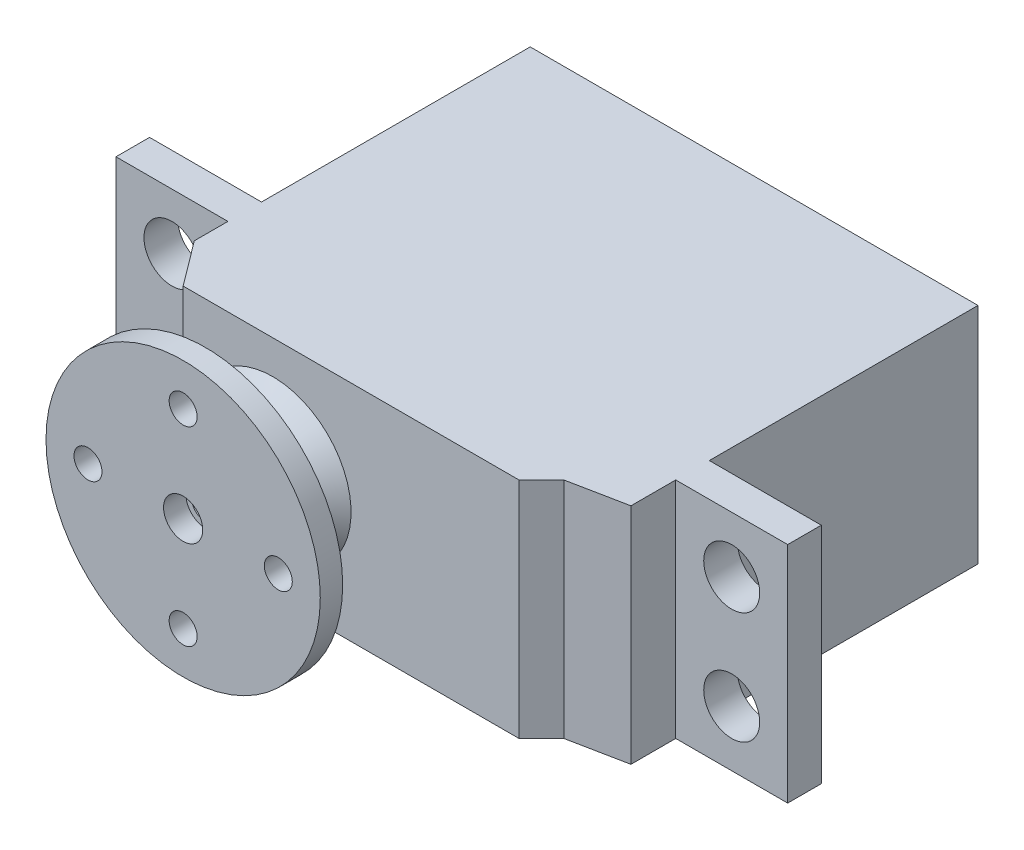
SolidWorks part; units mm, degrees
ref_plane "前视基准面" through (0, 0, 0) normal (0, 0, 1) x (1, 0, 0)
ref_plane "上视基准面" through (0, 0, 0) normal (0, 1, 0) x (1, 0, 0)
ref_plane "右视基准面" through (0, 0, 0) normal (1, 0, 0) x (0, 0, -1)
sketch "草图1" plane through (0, 0, 0) normal (0, 0, 1) x (1, 0, 0)
  line L1 (-20, -10) -> (20, -10)
  line L2 (-20, -10) -> (-20, 10)
  line L3 (-20, 10) -> (20, 10)
  line L4 (20, -10) -> (20, 10)
  line L5 (0, 10) -> (0, -10) construction
  line L6 (-20, 0) -> (20, 0) construction
  point P0 (0, 0)
  dimension "D1" = 40
  dimension "D2" = 20
extrude "凸台-拉伸1" add sketch "草图1" along normal blind 37
sketch "草图2" plane through (0, -10, 0) normal (0, -1, 0) x (1, 0, 0)
  line L0 (20, 34) -> (15, 35)
  line L1 (20, 37) -> (20, 0) construction
  line L2 (15, 35) -> (13, 37)
  line L3 (-20, 37) -> (20, 37) construction
  line L4 (13, 37) -> (20, 37)
  line L5 (20, 37) -> (20, 34)
  dimension "D1" = 3
  dimension "D2" = 2
  dimension "D3" = 2
  dimension "D4" = 5
extrude "切除-拉伸1" cut sketch "草图2" against normal through all
sketch "草图3" plane through (0, -10, 0) normal (0, -1, 0) x (1, 0, 0)
  line L0 (-20, 37) -> (-17, 37)
  line L1 (-20, 37) -> (13, 37) construction
  line L2 (-17, 37) -> (-20, 33)
  line L3 (-20, 37) -> (-20, 0) construction
  line L4 (-20, 33) -> (-20, 37)
  dimension "D1" = 3
  dimension "D2" = 4
extrude "切除-拉伸2" cut sketch "草图3" against normal through all
chamfer "倒角1" distance 3 angle 45 4 edges at (20, 0, 0) (0, 10, 0) (-20, 0, 0) (0, -10, 0)
sketch "草图4" plane through (0, 0, 37) normal (0, 0, 1) x (1, 0, 0)
  line L0 (-17, 10) -> (-17, -10) construction
  line L1 (13, 0) -> (-22.6233, 0) construction
  line L2 (13, 10) -> (13, -10) construction
  circle A0 centre (-9, 0) radius 7
  dimension "D1" = 14
  dimension "D2" = 8
extrude "凸台-拉伸2" add sketch "草图4" along normal blind 2
chamfer "倒角2" distance 2 angle 45 1 edges at (-2, 0, 39)
sketch "草图5" plane through (0, 0, 39) normal (0, 0, 1) x (1, 0, 0)
  circle A0 centre (-9, 0) radius 3
  dimension "D1" = 6
extrude "凸台-拉伸3" add sketch "草图5" along normal blind 4
ref_plane "基准面1" through (0, 0, 30) normal (0, 0, -1) x (-1, 0, 0)
sketch "草图6" plane through (0, 0, 30) normal (0, 0, -1) x (-1, 0, 0)
  line L0 (20, 10) -> (20, -10)
  line L1 (20, 10) -> (30, 10)
  line L2 (20, -10) -> (30, -10)
  line L3 (30, 10) -> (30, -10)
  line L4 (-20, 10) -> (-20, -10)
  line L5 (-20, 10) -> (-30, 10)
  line L6 (-20, -10) -> (-30, -10)
  line L7 (-30, 10) -> (-30, -10)
  dimension "D1" = 10
  dimension "D2" = 10
extrude "凸台-拉伸4" add sketch "草图6" along normal blind 3
sketch "草图7" plane through (0, 0, 30) normal (0, 0, 1) x (1, 0, 0)
  line L0 (-25, -8.7626) -> (-25, 14.1579) construction
  line L1 (-30, 10) -> (-20, 10) construction
  line L2 (-20, -10) -> (-30, -10) construction
  line L3 (-30, -10) -> (-30, 10) construction
  circle A0 centre (-25, 5) radius 2.5
  circle A1 centre (-25, -5) radius 2.5
  dimension "D1" = 5
  dimension "D2" = 5
  dimension "D3" = 5
  dimension "D4" = 5
  dimension "D5" = 5
extrude "切除-拉伸3" cut sketch "草图7" against normal blind 3
mirror "镜向1" about plane through (0, 0, 0) normal (1, 0, 0) of "切除-拉伸3"
hole_wizard "M3 螺纹孔1" positions "草图8" profile "草图9" tap size "M3" standard "GB"
sketch "草图8" plane through (0, 0, 43) normal (0, 0, 1) x (1, 0, 0)
  point P0 (-9, 0)
sketch "草图9" plane through (-9, 0, 43) normal (1, 0, 0) x (0, -1, 0)
  line L0 (0, 0) -> (0, 9.2511)
  line L1 (0, 9.2511) -> (1.25, 8.5)
  line L2 (1.25, 8.5) -> (1.25, 0)
  line L5 (1.25, 0) -> (0, 0)
  line L10 (0, 9.2511) -> (-1.25, 8.5) construction
  line L11 (0, -6.35) -> (0, 107.95) construction
  dimension "螺纹孔钻头直径" = 2.5
  dimension "螺纹孔钻头深度" = 8.5
  dimension "导头角度" = 118
sketch "草图10" plane through (0, 0, 43) normal (0, 0, 1) x (1, 0, 0)
  circle A0 centre (-9, 0) radius 12.25
  circle A1 centre (-9, 0) radius 8.5 construction
  circle A2 centre (-9, 8.5) radius 1.25
  circle A3 centre (-0.5, 0) radius 1.25
  circle A4 centre (-9, -8.5) radius 1.25
  circle A5 centre (-17.5, 0) radius 1.25
  circle A6 centre (-9, 0) radius 1.75
  point P14 (-9, 0)
  dimension "D1" = 24.5
  dimension "D2" = 17
  dimension "D3" = 2.5
  dimension "D5" = 3.5
  dimension "D4" = 4
extrude "凸台-拉伸5" add sketch "草图10" along normal blind 2
